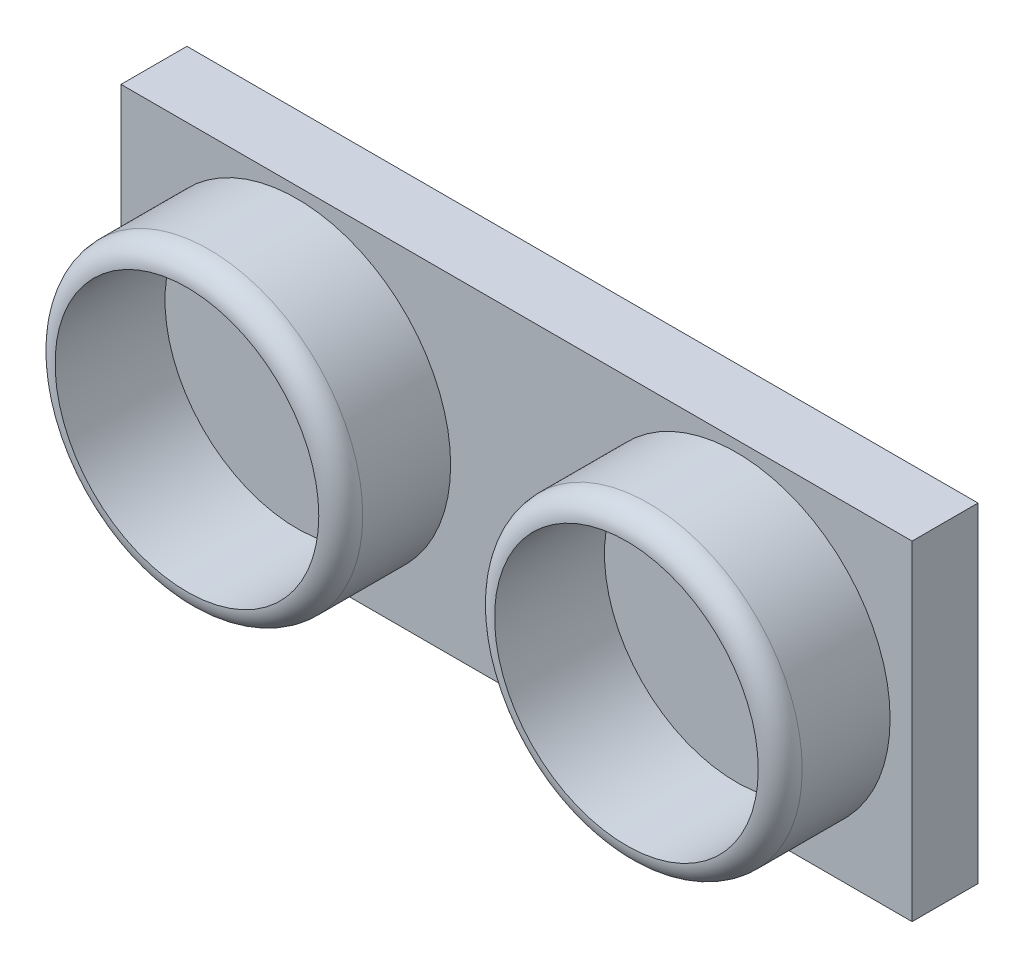
SolidWorks part; units mm, degrees
ref_plane "Front Plane" through (0, 0, 0) normal (0, 0, 1) x (1, 0, 0)
ref_plane "Top Plane" through (0, 0, 0) normal (0, 1, 0) x (1, 0, 0)
ref_plane "Right Plane" through (0, 0, 0) normal (1, 0, 0) x (0, 0, -1)
sketch "Sketch1" plane through (0, 0, 0) normal (0, 0, 1) x (1, 0, 0)
  line L1 (-18, 7.5) -> (18, 7.5)
  line L2 (-18, 7.5) -> (-18, -7.5)
  line L3 (-18, -7.5) -> (18, -7.5)
  line L4 (18, 7.5) -> (18, -7.5)
  line L5 (-18, 7.5) -> (18, -7.5) construction
  line L6 (-18, -7.5) -> (18, 7.5) construction
  point P0 (0, 0)
  dimension "D1" = 36
  dimension "D2" = 15
extrude "Boss-Extrude1" add sketch "Sketch1" along normal blind 3
sketch "Sketch2" plane through (0, 0, 3) normal (0, 0, 1) x (1, 0, 0)
  circle A0 centre (-10, 0) radius 7
  circle A1 centre (10, 0) radius 7
  circle A2 centre (-10, 0) radius 6
  circle A3 centre (10, 0) radius 6
extrude "Boss-Extrude2" add sketch "Sketch2" along normal blind 5
fillet "Fillet1" radius 1 2 edges at (17, 0, 8) (-3, 0, 8)
